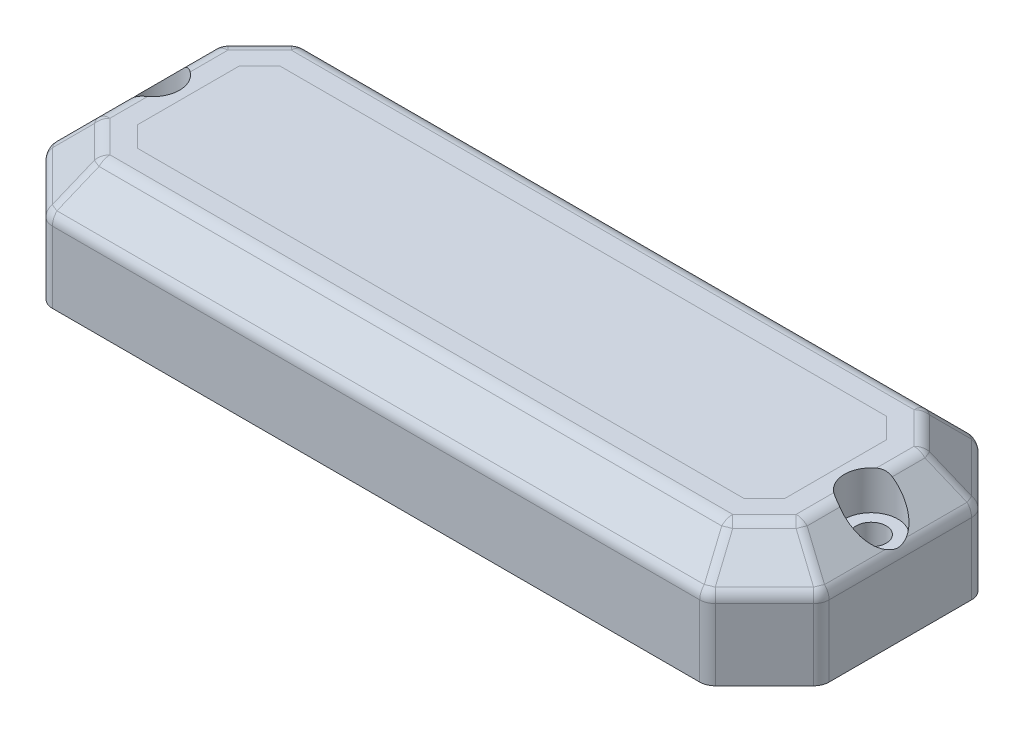
SolidWorks part; units mm, degrees
ref_plane "Front" through (0, 0, 0) normal (0, 0, 1) x (1, 0, 0)
ref_plane "Top" through (0, 0, 0) normal (0, 1, 0) x (1, 0, 0)
ref_plane "Right" through (0, 0, 0) normal (1, 0, 0) x (0, 0, -1)
sketch "Sketch2" plane through (0, 19.05, 0) normal (0, 1, 0) x (1, 0, 0)
  line L8 (-53.975, -22.225) -> (53.975, -22.225)
  line L9 (53.975, -22.225) -> (63.5, -12.7)
  line L10 (63.5, -12.7) -> (63.5, 12.7)
  line L11 (63.5, 12.7) -> (53.975, 22.225)
  line L12 (53.975, 22.225) -> (-53.975, 22.225)
  line L13 (-53.975, 22.225) -> (-63.5, 12.7)
  line L14 (-63.5, 12.7) -> (-63.5, -12.7)
  line L15 (-63.5, -12.7) -> (-53.975, -22.225)
  line L16 (-53.975, -22.225) -> (53.975, -22.225)
  line L17 (53.975, -22.225) -> (63.5, -12.7)
  line L18 (63.5, -12.7) -> (63.5, 12.7)
  line L19 (63.5, 12.7) -> (53.975, 22.225)
  line L20 (53.975, 22.225) -> (-53.975, 22.225)
  line L21 (-53.975, 22.225) -> (-63.5, 12.7)
  line L22 (-63.5, 12.7) -> (-63.5, -12.7)
  line L23 (-63.5, -12.7) -> (-53.975, -22.225)
  dimension "D1" = 0
extrude "Boss-Extrude1" add sketch "Sketch2" along normal blind 19.05
chamfer "Chamfer1" distance 6.35 angle 45 8 edges at (-63.5, 38.1, 0) (-58.7375, 38.1, -17.4625) (0, 38.1, -22.225) (58.7375, 38.1, -17.4625) (63.5, 38.1, 0) (58.7375, 38.1, 17.4625) (0, 38.1, 22.225) (-58.7375, 38.1, 17.4625)
shell "Shell2" thickness 2.54 removed face at (0, 19.05, 0)
fillet "Fillet1" radius 2.54 24 edges at (0, 38.1, -15.875) (54.2474, 38.1, -12.9724) (57.15, 38.1, 0) (54.2474, 38.1, 12.9724) (-57.15, 38.1, 0) (-54.2474, 38.1, -12.9724) (0, 38.1, 15.875) (-54.2474, 38.1, 12.9724) (-52.6599, 34.925, -19.05) (52.6599, 34.925, -19.05) (60.325, 34.925, -11.3849) (60.325, 34.925, 11.3849) (52.6599, 34.925, 19.05) (-52.6599, 34.925, 19.05) (-60.325, 34.925, -11.3849) (-60.325, 34.925, 11.3849) (-53.975, 25.4, 22.225) (53.975, 25.4, 22.225) (63.5, 25.4, 12.7) (63.5, 25.4, -12.7) (53.975, 25.4, -22.225) (-53.975, 25.4, -22.225) (-63.5, 25.4, -12.7) (-63.5, 25.4, 12.7)
fillet "Fillet2" radius 2.54 16 edges at (-63.3067, 31.8093, -12.6199) (-63.5, 31.75, 0) (-63.3067, 31.8093, 12.6199) (-58.7375, 31.75, 17.4625) (-53.8949, 31.8093, 22.0317) (0, 31.75, 22.225) (53.8949, 31.8093, 22.0317) (58.7375, 31.75, 17.4625) (63.3067, 31.8093, 12.6199) (63.5, 31.75, 0) (63.3067, 31.8093, -12.6199) (58.7375, 31.75, -17.4625) (53.8949, 31.8093, -22.0317) (0, 31.75, -22.225) (-53.8949, 31.8093, -22.0317) (-58.7375, 31.75, -17.4625)
sketch "Sketch4" plane through (0, 38.1, 0) normal (0, 1, 0) x (1, 0, 0)
  line L10 (-52.9229, 8.3188) -> (-52.9229, -8.3188)
  line L11 (-52.9229, 8.3188) -> (-52.9229, -8.3188)
  line L12 (-52.9229, -8.3188) -> (-49.5938, -11.6479)
  line L13 (-52.9229, -8.3188) -> (-49.5938, -11.6479)
  line L14 (-49.5938, -11.6479) -> (49.5938, -11.6479)
  line L15 (-49.5938, -11.6479) -> (49.5938, -11.6479)
  line L16 (49.5938, -11.6479) -> (52.9229, -8.3188)
  line L17 (49.5938, -11.6479) -> (52.9229, -8.3188)
  line L18 (52.9229, -8.3188) -> (52.9229, 8.3188)
  line L19 (52.9229, -8.3188) -> (52.9229, 8.3188)
  line L22 (52.9229, 8.3188) -> (49.5938, 11.6479)
  line L23 (52.9229, 8.3188) -> (49.5938, 11.6479)
  line L32 (49.5938, 11.6479) -> (-49.5938, 11.6479)
  line L33 (49.5938, 11.6479) -> (-49.5938, 11.6479)
  line L34 (-49.5938, 11.6479) -> (-52.9229, 8.3188)
  line L35 (-49.5938, 11.6479) -> (-52.9229, 8.3188)
  dimension "D1" = 3.175
split line "Split Line1"
sketch "Sketch5" plane through (0, 19.05, 0) normal (0, -1, 0) x (1, 0, 0)
  line L1 (-52.9229, 8.3188) -> (-52.9229, -8.3188) construction
  line L2 (52.9229, -8.3188) -> (52.9229, 8.3188) construction
  line L11 (60.96, 11.6479) -> (60.96, -11.6479) construction
  line L12 (60.96, -4.7625) -> (52.9229, -4.7625)
  line L19 (-52.9229, -4.7625) -> (-60.96, -4.7625)
  line L20 (-52.9229, -4.7625) -> (-52.9229, 4.7625)
  line L22 (60.96, -4.7625) -> (60.96, 4.7625)
  line L24 (-52.9229, 4.7625) -> (-60.96, 4.7625)
  line L25 (-60.96, -4.7625) -> (-60.96, 4.7625)
  line L26 (-52.9229, -4.7625) -> (-60.96, 4.7625) construction
  line L27 (-52.9229, 4.7625) -> (-60.96, -4.7625) construction
  line L28 (-60.96, -11.6479) -> (-60.96, 11.6479) construction
  line L29 (60.96, 4.7625) -> (52.9229, 4.7625)
  line L30 (52.9229, -4.7625) -> (52.9229, 4.7625)
  line L31 (60.96, -4.7625) -> (52.9229, 4.7625) construction
  line L32 (60.96, 4.7625) -> (52.9229, -4.7625) construction
  point P0 (56.9414, 0)
  point P9 (-56.9414, 0)
  line M6 (-60.96, -11.6479) -> (-60.96, 11.6479)
  line M10 (60.96, 11.6479) -> (60.96, -11.6479)
  dimension "D1" = 9.525
extrude "Boss-Extrude7" add sketch "Sketch5" against normal up to next contours L20 L24 L19 M6 | L30 L12 L29 M10 region at (56.9414, 19.05, 0) region at (-56.9414, 19.05, 0)
hole_wizard "CBORE for #8 Button Head Cap Screw1" positions "Sketch7" profile "Sketch8" counterbore size "#8" standard "ANSI Inch" end condition through all
sketch "Sketch7" plane through (0, 38.1, 0) normal (0, 1, 0) x (1, 0, 0)
  point P13 (-58.7375, 0)
  point P15 (58.7375, 0)
sketch "Sketch8" plane through (-58.7375, 38.1, 0) normal (1, 0, 0) x (0, 0, 1)
  line L0 (0, 0) -> (0, 19.05)
  line L1 (0, 19.05) -> (2.4574, 19.05)
  line L3 (2.4574, 19.05) -> (2.4575, 6.35)
  line L4 (2.4575, 6.35) -> (4.3663, 6.35)
  line L5 (4.3663, 6.35) -> (4.3663, 0)
  line L7 (4.3663, 0) -> (0, 0)
  line L11 (0, -6.35) -> (0, 107.95) construction
  dimension "Thru Hole Dia." = 4.9149
  dimension "Thru Hole Depth" = 19.05
  dimension "C'Bore Dia." = 8.7325
  dimension "C'Bore Depth" = 6.35
fillet "Fillet3" radius 2.54 16 edges at (-60.96, 24.8739, -11.6479) (-52.9229, 24.8739, -19.685) (52.9229, 24.8739, -19.685) (60.96, 24.8739, -11.6479) (60.96, 24.8739, -4.7625) (52.9229, 27.305, -4.7625) (52.9229, 27.305, 4.7625) (60.96, 24.8739, 4.7625) (60.96, 24.8739, 11.6479) (52.9229, 24.8739, 19.685) (-52.9229, 24.8739, 19.685) (-60.96, 24.8739, 11.6479) (-60.96, 24.8739, 4.7625) (-52.9229, 27.305, 4.7625) (-52.9229, 27.305, -4.7625) (-60.96, 24.8739, -4.7625)
